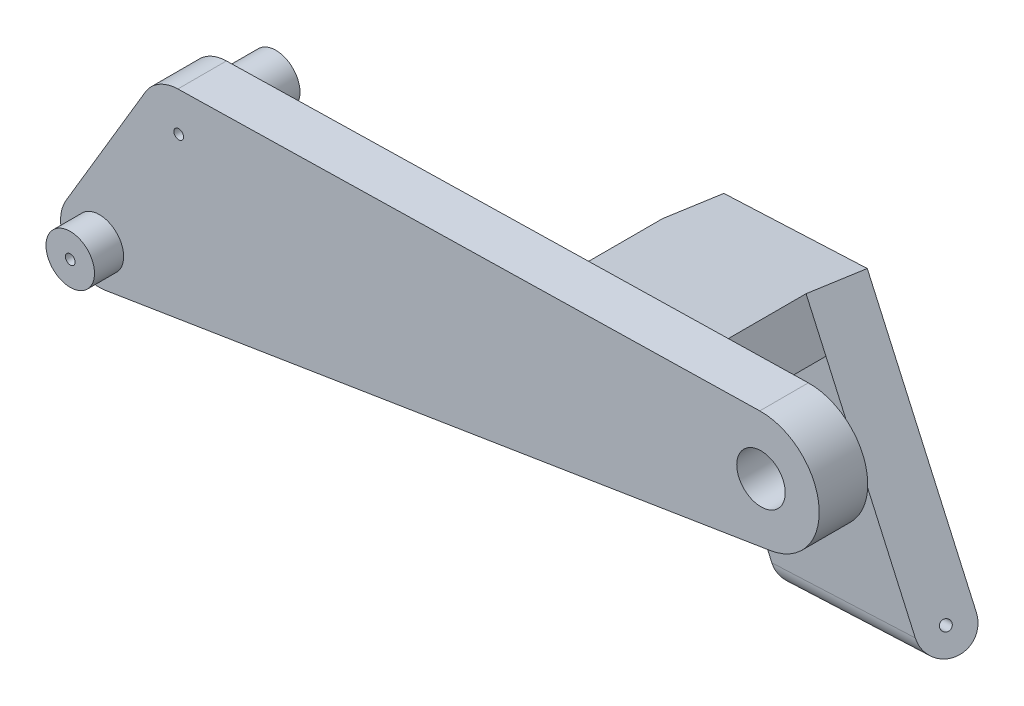
SolidWorks part; units mm, degrees
material "ABS"
ref_plane "Front Plane" through (0, 0, 0) normal (0, 0, 1) x (1, 0, 0)
ref_plane "Top Plane" through (0, 0, 0) normal (0, 1, 0) x (1, 0, 0)
ref_plane "Right Plane" through (0, 0, 0) normal (1, 0, 0) x (0, 0, -1)
sketch "Sketch2" plane through (0, 0, 0) normal (0, 0, 1) x (1, 0, 0)
  line L0 (-8.1718, -13.7558) -> (0, 0)
  line L1 (0, 0) -> (60, -0.7468)
  dimension "D1" = 60
  dimension "D2" = 16
  dimension "D3" = 120
sketch "Sketch3" plane through (0, 0, 0) normal (0, 0, 1) x (1, 0, 0)
  line L0 (-11.6108, -11.7128) -> (-3.4389, 2.043)
  line L1 (-0.0836, 3.9991) -> (59.8747, 5.2519)
  line L2 (60.9544, -6.6704) -> (-7.5356, -17.7048)
  circle A0 centre (-8.1718, -13.7558) radius 2.5
  arc A1 (-11.6108, -11.7128) -> (-7.5356, -17.7048) centre (-8.1718, -13.7558) ccw
  circle A2 centre (0, 0) radius 2.5
  arc A3 (-0.0836, 3.9991) -> (-3.4389, 2.043) centre (0, 0) ccw
  arc A4 (60.9544, -6.6704) -> (59.8747, 5.2519) centre (60, -0.7468) ccw
  dimension "D1" = 5
  dimension "D2" = 8
  dimension "D3" = 5
  dimension "D4" = 8
  dimension "D5" = 12
extrude "Boss-Extrude1" add sketch "Sketch3" along normal blind 5
sketch "Sketch4" plane through (0, 0, 5) normal (0, 0, 1) x (1, 0, 0)
  circle A0 centre (0, 0) radius 2.5
  circle A1 centre (0, 0) radius 0.5
  dimension "D1" = 1
  dimension "D2" = 5
extrude "Boss-Extrude2" add sketch "Sketch4" against normal blind 10
sketch "Sketch5" plane through (0, 0, 0) normal (0, 0, -1) x (-1, 0, 0)
  circle A0 centre (8.1718, -13.7558) radius 2.5
  circle A1 centre (8.1718, -13.7558) radius 0.5
  dimension "D1" = 1
  dimension "D2" = 5
extrude "Boss-Extrude3" add sketch "Sketch5" against normal blind 8
sketch "Sketch6" plane through (0, 0, 0) normal (0, 0, -1) x (-1, 0, 0)
  line L0 (0, 0) -> (-60, -0.7468) construction
  circle A1 centre (-60, -0.7468) radius 2.5
  dimension "D1" = 5
  dimension "D2" = 0
extrude "Cut-Extrude1" cut sketch "Sketch6" against normal blind 5
sketch "Sketch7" plane through (0, 0, 0) normal (0, 0, -1) x (-1, 0, 0)
  line L5 (-26.9115, -12.1551) -> (-52.4604, -0.6985)
  line L6 (-26.9115, -12.1551) -> (-24.8656, -7.5928)
  line L7 (-52.4604, -0.6985) -> (-50.4146, 3.8638)
  line L8 (-24.8656, -7.5928) -> (-50.4146, 3.8638)
  line L9 (7.5356, -17.7048) -> (-60.9544, -6.6704) construction
  dimension "D1" = 5
  dimension "D2" = 35
  dimension "D3" = 28
  dimension "D4" = 15
extrude "Boss-Extrude4" add sketch "Sketch7" along normal blind 20
sketch "Sketch28" plane through (6.9976, -15.6051, 0) normal (-0.4092, 0.9125, 0) x (0.9125, 0.4092, 0)
  line L0 (19.5823, 20) -> (47.5823, 20)
  line L1 (47.5823, 20) -> (47.5823, 9.2297)
  line L2 (47.5823, 20) -> (47.5823, 0) construction
  line L3 (47.5823, 9.2297) -> (19.5823, 20)
  dimension "D1" = 30
extrude "Cut-Extrude13" cut sketch "Sketch28" against normal blind 5
sketch "Sketch29" plane through (8.4179, 3.7747, -23.9838) normal (0.3276, 0.1469, -0.9333) x (-0.9448, 0.0409, -0.3252)
  line L0 (-17.2993, -10.7868) -> (-44.4713, 1.9287)
  line L1 (-17.2993, -10.7868) -> (-30.0147, -37.9588)
  line L2 (-44.4713, 1.9287) -> (-57.1867, -25.2433)
  line L3 (-30.0147, -37.9588) -> (-57.1867, -25.2433)
  dimension "D1" = 30
extrude "Boss-Extrude10" add sketch "Sketch29" along normal blind 5
sketch "Sketch30" plane through (9.4502, 4.2376, 3.9838) normal (-0.8516, -0.3819, -0.359) x (-0.3402, -0.1182, 0.9329)
  line L2 (-32.1581, -46.117) -> (-27.1606, -46.2737) construction
  line L3 (-32.1581, -46.117) -> (-31.2178, -16.1317) construction
  circle A0 centre (-29.581, -43.6966) radius 0.5
  dimension "D1" = 1
  dimension "D2" = 2.5
  dimension "D3" = 2.5
extrude "Cut-Extrude14" cut sketch "Sketch30" against normal blind 30
fillet "Fillet5" 2 edges at (51.5529, -28.5038, -19.2815) (49.915, -29.2383, -14.6148) type full round first side face at (45.4155, -14.8169, -19.2815) second side face at (44.8005, -17.8325, -14.6148) middle face at (50.734, -28.8711, -16.9482)
